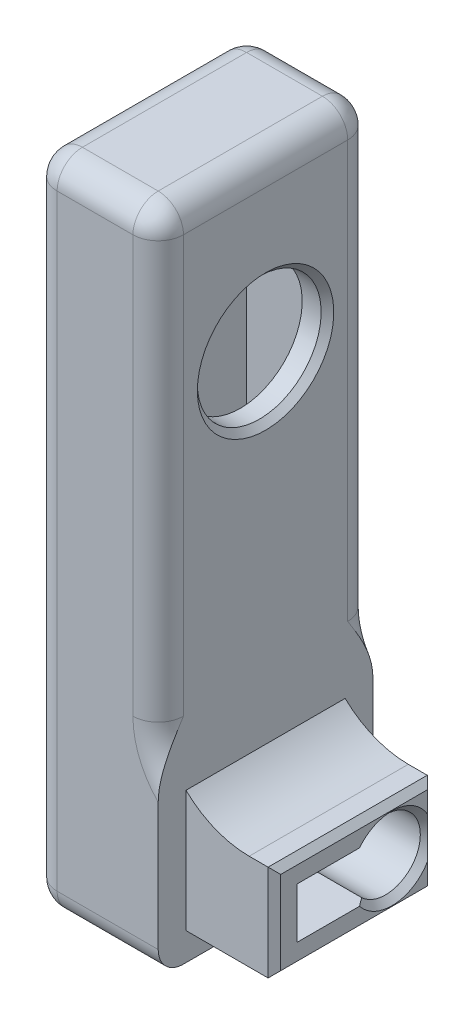
SolidWorks part; units mm, degrees
ref_plane "Front Plane" through (0, 0, 0) normal (0, 0, 1) x (1, 0, 0)
ref_plane "Top Plane" through (0, 0, 0) normal (0, 1, 0) x (1, 0, 0)
ref_plane "Right Plane" through (0, 0, 0) normal (1, 0, 0) x (0, 0, -1)
sketch "Sketch1" plane through (0, 0, 0) normal (1, 0, 0) x (0, 0, -1)
  line L1 (0, 0) -> (13, 0)
  line L2 (0, 0) -> (0, 8)
  line L3 (0, 8) -> (13, 8)
  line L4 (13, 0) -> (13, 8)
  dimension "D2" = 8
  dimension "D3" = 13
extrude "Boss-Extrude1" add sketch "Sketch1" along normal blind 7
sketch "Sketch2" plane through (0, 0, 0) normal (0, -1, 0) x (-1, 0, 0)
  line L1 (0, -2) -> (10, -2)
  line L2 (0, -2) -> (0, 15)
  line L3 (0, 15) -> (10, 15)
  line L4 (10, -2) -> (10, 15)
  line L5 (0, 0) -> (0, -2) construction
  line L6 (0, 13) -> (0, 15) construction
  dimension "D1" = 10
  dimension "D2" = 17
extrude "Boss-Extrude2" add sketch "Sketch2" against normal blind 50 and the other way blind 2
sketch "Sketch3" plane through (7, 0, 0) normal (1, 0, 0) x (0, 0, -1)
  line L0 (-2, -2) -> (-2, 50) construction
  line L1 (-2, 8) -> (15, 8)
  line L2 (-2, 8) -> (-2, 10)
  line L3 (-2, 10) -> (15, 10)
  line L4 (15, 8) -> (15, 10)
  line L5 (15, -2) -> (15, 50) construction
  line L6 (13, 8) -> (0, 8) construction
  dimension "D1" = 2
extrude "Boss-Extrude3" add sketch "Sketch3" against normal up to next
fillet "Fillet4" radius 5 1 edges at (0, 10, -6.5)
fillet "Fillet3" radius 2 15 edges at (-5, 50, -15) (-10, 50, -6.5) (-5, 50, 2) (0, 50, -6.5) (-10, 24, 2) (-5, -2, 2) (-10, 24, -15) (-10, -2, -6.5) (-5, -2, -15) (6, 10, -15) (1.4645, 11.4645, -15) (6, 10, 2) (1.4645, 11.4645, 2) (0, 32.5, -15) (0, 32.5, 2)
sketch "Sketch4" plane through (7, 0, 0) normal (1, 0, 0) x (0, 0, -1)
  line L1 (-2, 8) -> (15, 8)
  line L2 (-2, 8) -> (-2, 15)
  line L3 (-2, 15) -> (15, 15)
  line L4 (15, 8) -> (15, 15)
extrude "Cut-Extrude1" cut sketch "Sketch4" against normal up to surface (7 mm away) up to face at (0, 31.5, -6.5)
sketch "Sketch5" plane through (0, 0, -13) normal (0, 0, -1) x (-1, 0, 0)
  line L0 (0, 8) -> (-5, 8)
  line L1 (-7, 8) -> (0, 8) construction
  line L2 (0, 15) -> (0, 10.101) construction
  line L3 (0, 10.101) -> (0, 8)
  arc A0 (-5, 8) -> (0, 10.101) centre (-5, 15) ccw
  arc A1 (0, 10.101) -> (2, 15) centre (-5, 15) ccw construction
extrude "Boss-Extrude4" add sketch "Sketch5" against normal up to surface (13 mm away) up to face at (3.5, 4, 0)
shell "Shell1" thickness 2 removed face at (7, 4, -6.5)
sketch "Sketch6" plane through (0, 0, 0) normal (1, 0, 0) x (0, 0, -1)
  line L0 (13, 48) -> (0, 48) construction
  line L1 (0, 50) -> (13, 50) construction
  circle A0 centre (6.5, 36.75) radius 4.9
  point P4 (6.5, 48)
  dimension "D2" = 9.8
  dimension "D1" = 13.25
extrude "Cut-Extrude2" cut sketch "Sketch6" against normal up to next
chamfer "Chamfer1" distance 0.5 angle 45 1 edges at (0, 36.75, -11.4)
sketch "Sketch7" plane through (7, 0, 0) normal (1, 0, 0) x (0, 0, -1)
  line L0 (11, 2) -> (11, 6) construction
  circle A0 centre (9.5, 4) radius 2.75
  point P4 (11, 4)
  dimension "D1" = 5.5
  dimension "D2" = 1.5
extrude "Cut-Extrude3" cut sketch "Sketch7" against normal up to surface (15 mm away) up to face at (-8, 24, -6.5)
sketch "Sketch8" plane through (7, 0, 0) normal (1, 0, 0) x (0, 0, -1)
  circle A0 centre (9.5, 4) radius 1.75
  arc A1 (7.6125, 2) -> (7.6125, 6) centre (9.5, 4) ccw construction
  dimension "D1" = 3.5
extrude "Cut-Extrude4" cut sketch "Sketch8" against normal through all
sketch "Sketch9" plane through (7, 0, 0) normal (1, 0, 0) x (0, 0, -1)
  line L0 (0, 10.101) -> (0.2, 10.101)
  line L1 (0, 0) -> (13, 0)
  line L2 (0, 0) -> (0, 10.101)
  line L3 (0, 10.101) -> (13, 10.101) construction
  line L4 (13, 0) -> (13, 10.101)
  line L5 (0.2, 10.101) -> (0.2, 0.2)
  line L6 (0.2, 0.2) -> (12.8, 0.2)
  line L7 (12.8, 0.2) -> (12.8, 10.101)
  line L8 (12.8, 10.101) -> (13, 10.101)
  line L9 (0.2, 0.2) -> (0.2, 0) construction
  dimension "D1" = 0.2
extrude "Cut-Extrude5" cut sketch "Sketch9" against normal up to surface (7 mm away) up to face at (0, 36.75, -1.1)
sketch "Sketch10" plane through (0, 0, -0.2) normal (0, 0, 1) x (1, 0, 0)
  line L0 (7, 8) -> (5, 8)
  line L1 (7, 8) -> (7, 7.8)
  line L2 (7, 0.2) -> (7, 8) construction
  line L3 (7, 7.8) -> (5, 7.8)
  line L4 (0, 0) -> (0, 10.101) construction
  line L5 (0, 10.101) -> (0, 9.8193)
  arc A0 (5, 8) -> (0, 10.101) centre (5, 15) cw
  arc A1 (5, 7.8) -> (0, 9.8193) centre (5, 15) cw
  arc A2 (0, 10.101) -> (5, 8) centre (5, 15) ccw construction
  dimension "D1" = 0.2
extrude "Cut-Extrude6" cut sketch "Sketch10" against normal up to surface (12.6 mm away) up to face at (3.7577, 5.1994, -12.8)
chamfer "Chamfer2" distance 0.5 angle 45 5 edges at (7, 4, -12.25) (7, 4, -0.2) (7, 0.2, -6.5) (7, 4, -12.8) (7, 7.8, -6.5)
